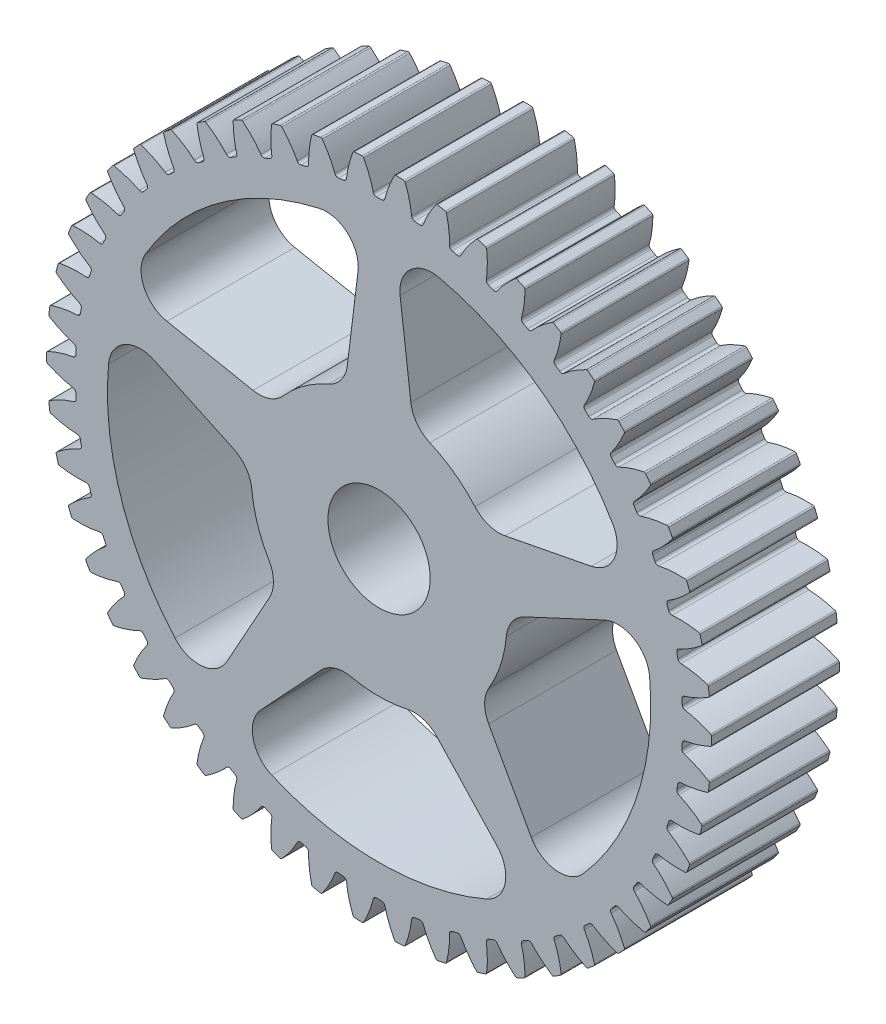
SolidWorks part; units mm, degrees
material "Alloy Steel"
ref_plane "Front" through (0, 0, 0) normal (0, 0, 1) x (1, 0, 0)
ref_plane "Top" through (0, 0, 0) normal (0, 1, 0) x (1, 0, 0)
ref_plane "Right" through (0, 0, 0) normal (1, 0, 0) x (0, 0, -1)
sketch "Sketch1" plane through (0, 0, 0) normal (0, 0, 1) x (1, 0, 0)
  circle A0 centre (0, 0) radius 33.02
  dimension "OutsideDiameter" = 66.04
extrude "Boss-Extrude1" add sketch "Sketch1" along normal blind 12.7
sketch "Sketch3" plane through (0, 0, 0) normal (0, 0, 1) x (1, 0, 0)
  line L0 (0, 0) -> (43.7181, 0) construction
  line L2 (0, 0) -> (-0.498, 30.1584) construction
  line L3 (0, 0) -> (0.498, 30.1584) construction
  line L4 (0.498, 30.1584) -> (0.4926, 29.8312) construction
  line L5 (0, 0) -> (0, 61.276) construction
  line L6 (-0.498, 30.1584) -> (-0.4926, 29.8312) construction
  circle A0 centre (0, 0) radius 33.02 construction
  circle A1 centre (0, 0) radius 31.75 construction
  circle A2 centre (0, 0) radius 29.8352 construction
  arc A3 (0.498, 30.1584) -> (-0.498, 30.1584) centre (0, 0) ccw construction
  arc A5 (1.5817, 32.9821) -> (-1.5817, 32.9821) centre (0, 0) ccw
  spline S0 degree 4 poles (-0.4926, 29.8312) (-0.4927, 29.8361) (-0.4933, 29.85) (-0.4949, 29.8763) (-0.4983, 29.9192) (-0.504, 29.9738) (-0.5128, 30.0443) (-0.5251, 30.1273) (-0.5406, 30.2184) (-0.5595, 30.3176) (-0.5803, 30.4164) (-0.6028, 30.5149) (-0.6268, 30.6129) (-0.6577, 30.7316) (-0.6973, 30.8738) (-0.7475, 31.0397) (-0.8089, 31.2277) (-0.8762, 31.4191) (-0.9464, 31.6071) (-1.0218, 31.7967) (-1.098, 31.98) (-1.1818, 32.1701) (-1.2615, 32.3454) (-1.3559, 32.5413) (-1.4337, 32.6994) (-1.5417, 32.9075) (-1.6071, 33.0302) (-1.6856, 33.1737) (-1.7214, 33.2374) (-1.7435, 33.2766) knots 0 0 0 0 0 0.005377 0.015084 0.028532 0.04661 0.064855 0.092111 0.119476 0.146842 0.174209 0.201575 0.228941 0.256307 0.307035 0.361767 0.4165 0.471232 0.525964 0.580697 0.635429 0.690161 0.744894 0.799626 0.854358 0.909091 0.954545 1 1 1 1 1 construction
  spline S1 degree 4 poles (-0.4926, 29.8312) (-0.4927, 29.8361) (-0.4933, 29.85) (-0.4949, 29.8763) (-0.4983, 29.9192) (-0.504, 29.9738) (-0.5128, 30.0443) (-0.5251, 30.1273) (-0.5406, 30.2184) (-0.5595, 30.3176) (-0.5803, 30.4164) (-0.6028, 30.5149) (-0.6268, 30.6129) (-0.6577, 30.7316) (-0.6973, 30.8738) (-0.7475, 31.0397) (-0.8089, 31.2277) (-0.8762, 31.4191) (-0.9464, 31.6071) (-1.0218, 31.7967) (-1.098, 31.98) (-1.1818, 32.1701) (-1.2615, 32.3454) (-1.3559, 32.5413) (-1.4337, 32.6994) (-1.5183, 32.8623) (-1.5601, 32.9416) (-1.5817, 32.9821) knots 0 0 0 0 0 0.005377 0.015084 0.028532 0.04661 0.064855 0.092111 0.119476 0.146842 0.174209 0.201575 0.228941 0.256307 0.307035 0.361767 0.4165 0.471232 0.525964 0.580697 0.635429 0.690161 0.744894 0.799626 0.854358 0.909091 0.909091 0.909091 0.909091 0.909091
  spline S2 degree 4 poles (0.4926, 29.8312) (0.4927, 29.8361) (0.4933, 29.85) (0.4949, 29.8763) (0.4983, 29.9192) (0.504, 29.9738) (0.5128, 30.0443) (0.5251, 30.1273) (0.5406, 30.2184) (0.5595, 30.3176) (0.5803, 30.4164) (0.6028, 30.5149) (0.6268, 30.6129) (0.6577, 30.7316) (0.6973, 30.8738) (0.7475, 31.0397) (0.8089, 31.2277) (0.8762, 31.4191) (0.9464, 31.6071) (1.0218, 31.7967) (1.098, 31.98) (1.1818, 32.1701) (1.2615, 32.3454) (1.3559, 32.5413) (1.4337, 32.6994) (1.5417, 32.9075) (1.6071, 33.0302) (1.6856, 33.1737) (1.7214, 33.2374) (1.7435, 33.2766) knots 0 0 0 0 0 0.005377 0.015084 0.028532 0.04661 0.064855 0.092111 0.119476 0.146842 0.174209 0.201575 0.228941 0.256307 0.307035 0.361767 0.4165 0.471232 0.525964 0.580697 0.635429 0.690161 0.744894 0.799626 0.854358 0.909091 0.954545 1 1 1 1 1 construction
  spline S3 degree 4 poles (0.4926, 29.8312) (0.4927, 29.8361) (0.4933, 29.85) (0.4949, 29.8763) (0.4983, 29.9192) (0.504, 29.9738) (0.5128, 30.0443) (0.5251, 30.1273) (0.5406, 30.2184) (0.5595, 30.3176) (0.5803, 30.4164) (0.6028, 30.5149) (0.6268, 30.6129) (0.6577, 30.7316) (0.6973, 30.8738) (0.7475, 31.0397) (0.8089, 31.2277) (0.8762, 31.4191) (0.9464, 31.6071) (1.0218, 31.7967) (1.098, 31.98) (1.1818, 32.1701) (1.2615, 32.3454) (1.3559, 32.5413) (1.4337, 32.6994) (1.5183, 32.8623) (1.5601, 32.9416) (1.5817, 32.9821) knots 0 0 0 0 0 0.005377 0.015084 0.028532 0.04661 0.064855 0.092111 0.119476 0.146842 0.174209 0.201575 0.228941 0.256307 0.307035 0.361767 0.4165 0.471232 0.525964 0.580697 0.635429 0.690161 0.744894 0.799626 0.854358 0.909091 0.909091 0.909091 0.909091 0.909091
  dimension "OutsideDiameter" = 66.04
  dimension "PitchCircle" = 63.5
  dimension "BaseCircle" = 59.6705
  dimension "DedendumCircle" = 60.325
sketch "DCLTBC" [suppressed] plane through (0, 0, 0) normal (0, 0, 1) x (1, 0, 0)
  line L0 (0, 0) -> (41.04, 0) construction
  line L1 (-0.5882, 26.2434) -> (-0.5952, 26.5563) construction
  line L2 (0.5882, 26.2434) -> (0.5952, 26.5563) construction
  line L3 (-0.5936, 26.4814) -> (-0.5952, 26.5563)
  line L4 (0.5936, 26.4814) -> (0.5952, 26.5563)
  line L5 (0, 0) -> (0, 104.9356) construction
  circle A0 centre (0, 0) radius 28.5
  circle A1 centre (0, 0) radius 27.5 construction
  circle A2 centre (0, 0) radius 26.563 construction
  arc A3 (0.5882, 26.2434) -> (-0.5882, 26.2434) centre (0, 0) ccw construction
  arc A4 (0.3512, 26.2477) -> (-0.3512, 26.2477) centre (0, 0) ccw
  arc A5 (-0.5936, 26.4814) -> (-0.3512, 26.2477) centre (-0.3544, 26.4868) ccw
  arc A7 (0.5936, 26.4814) -> (0.3512, 26.2477) centre (0.3544, 26.4868) cw
  spline S0 degree 4 poles (-999.0854, -27.9057) (-10.5882, 25.1883) (-0.7108, 25.7707) (-0.5671, 26.1913) (-0.5985, 26.609) (-0.6016, 26.6417) (-0.6063, 26.6839) (-0.6128, 26.7337) (-0.6209, 26.7885) (-0.6307, 26.8481) (-0.6414, 26.9075) (-0.653, 26.9669) (-0.6654, 27.026) (-0.6812, 27.0976) (-0.7015, 27.1836) (-0.7271, 27.2842) (-0.7584, 27.3983) (-0.7927, 27.5147) (-0.8284, 27.6294) (-0.8667, 27.7454) (-0.9054, 27.8577) (-0.948, 27.9745) (-0.9884, 28.0824) (-1.0364, 28.2034) (-1.2469, 28.7251) (-2.0615, 30.5023) (8.679, 5.7048) (-401.0337, 945.0216) knots -0.712101 -0.712101 -0.712101 -0.712101 -0.712101 0.005377 0.015084 0.028532 0.04661 0.064855 0.092111 0.119476 0.146842 0.174209 0.201575 0.228941 0.256307 0.307035 0.361767 0.4165 0.471232 0.525964 0.580697 0.635429 0.690161 0.744894 0.799626 0.854358 1.858481 1.858481 1.858481 1.858481 1.858481 only from (-0.5952, 26.5563) to (-1.151, 28.4767) construction
  spline S1 degree 4 poles (999.0854, -27.9056) (10.5882, 25.1883) (0.7108, 25.7707) (0.5671, 26.1913) (0.5985, 26.609) (0.6016, 26.6417) (0.6063, 26.6839) (0.6128, 26.7337) (0.6209, 26.7885) (0.6307, 26.8481) (0.6414, 26.9075) (0.653, 26.9669) (0.6654, 27.026) (0.6812, 27.0976) (0.7015, 27.1836) (0.7271, 27.2842) (0.7584, 27.3983) (0.7927, 27.5147) (0.8284, 27.6294) (0.8667, 27.7454) (0.9054, 27.8577) (0.948, 27.9745) (0.9884, 28.0824) (1.0364, 28.2034) (1.2469, 28.7251) (2.0615, 30.5023) (-8.679, 5.7048) (401.0337, 945.0216) knots -0.712101 -0.712101 -0.712101 -0.712101 -0.712101 0.005377 0.015084 0.028532 0.04661 0.064855 0.092111 0.119476 0.146842 0.174209 0.201575 0.228941 0.256307 0.307035 0.361767 0.4165 0.471232 0.525964 0.580697 0.635429 0.690161 0.744894 0.799626 0.854358 1.858481 1.858481 1.858481 1.858481 1.858481 only from (0.5952, 26.5563) to (1.151, 28.4767) construction
  spline S2 degree 4 poles (-0.5952, 26.5563) (-0.5953, 26.5593) (-0.5957, 26.5676) (-0.5966, 26.5833) (-0.5985, 26.609) (-0.6016, 26.6417) (-0.6063, 26.6839) (-0.6128, 26.7337) (-0.6209, 26.7885) (-0.6307, 26.8481) (-0.6414, 26.9075) (-0.653, 26.9669) (-0.6654, 27.026) (-0.6812, 27.0976) (-0.7015, 27.1836) (-0.7271, 27.2842) (-0.7584, 27.3983) (-0.7927, 27.5147) (-0.8284, 27.6294) (-0.8667, 27.7454) (-0.9054, 27.8577) (-0.948, 27.9745) (-0.9884, 28.0824) (-1.0364, 28.2034) (-1.0758, 28.3012) (-1.1188, 28.4023) (-1.14, 28.4516) (-1.151, 28.4767) knots 0 0 0 0 0 0.005377 0.015084 0.028532 0.04661 0.064855 0.092111 0.119476 0.146842 0.174209 0.201575 0.228941 0.256307 0.307035 0.361767 0.4165 0.471232 0.525964 0.580697 0.635429 0.690161 0.744894 0.799626 0.854358 0.909091 0.909091 0.909091 0.909091 0.909091
  spline S3 degree 4 poles (0.5952, 26.5563) (0.5953, 26.5593) (0.5957, 26.5676) (0.5966, 26.5833) (0.5985, 26.609) (0.6016, 26.6417) (0.6063, 26.6839) (0.6128, 26.7337) (0.6209, 26.7885) (0.6307, 26.8481) (0.6414, 26.9075) (0.653, 26.9669) (0.6654, 27.026) (0.6812, 27.0976) (0.7015, 27.1836) (0.7271, 27.2842) (0.7584, 27.3983) (0.7927, 27.5147) (0.8284, 27.6294) (0.8667, 27.7454) (0.9054, 27.8577) (0.948, 27.9745) (0.9884, 28.0824) (1.0364, 28.2034) (1.0758, 28.3012) (1.1188, 28.4023) (1.14, 28.4516) (1.151, 28.4767) knots 0 0 0 0 0 0.005377 0.015084 0.028532 0.04661 0.064855 0.092111 0.119476 0.146842 0.174209 0.201575 0.228941 0.256307 0.307035 0.361767 0.4165 0.471232 0.525964 0.580697 0.635429 0.690161 0.744894 0.799626 0.854358 0.909091 0.909091 0.909091 0.909091 0.909091
  dimension "OutsideDiameter" = 66.04
  dimension "PitchCircle" = 63.5
  dimension "BaseCircle" = 59.6705
  dimension "D1" = 0.3238
extrude "Cut-Extrude-DCLTBC" [suppressed] cut sketch "DCLTBC" along normal through all contours L4 S3 A0 S2 L3 A5 A4 A7
fillet "Fillet-DCLTBC" [suppressed] radius 0.1619
pattern_circular "CirPattern-DCLTBC" [suppressed] count 50 over 360 of bodies 111
sketch "DCGTBC" plane through (0, 0, 0) normal (0, 0, 1) x (1, 0, 0)
  line L0 (0, 0) -> (41.04, 0) construction
  line L5 (0, 0) -> (0, 104.9356) construction
  circle A0 centre (0, 0) radius 33.02
  circle A1 centre (0, 0) radius 31.75 construction
  circle A2 centre (0, 0) radius 29.8352 construction
  arc A3 (0.498, 30.1584) -> (-0.498, 30.1584) centre (0, 0) ccw construction
  arc A5 (0.2614, 30.1614) -> (0.5806, 30.4159) centre (0.2642, 30.4852) ccw
  arc A7 (-0.5806, 30.4159) -> (-0.2614, 30.1614) centre (-0.2642, 30.4852) ccw
  arc A11 (0.2614, 30.1614) -> (-0.2614, 30.1614) centre (0, 0) ccw
  spline S2 degree 4 poles (-999.5536, -12.7278) (-12.5544, 28.0053) (-0.6553, 28.7383) (-0.4506, 29.3302) (-0.4983, 29.9192) (-0.504, 29.9738) (-0.5128, 30.0443) (-0.5251, 30.1273) (-0.5406, 30.2184) (-0.5595, 30.3176) (-0.5803, 30.4164) (-0.6028, 30.5149) (-0.6268, 30.6129) (-0.6577, 30.7316) (-0.6973, 30.8738) (-0.7475, 31.0397) (-0.8089, 31.2277) (-0.8762, 31.4191) (-0.9464, 31.6071) (-1.0218, 31.7967) (-1.098, 31.98) (-1.1818, 32.1701) (-1.2615, 32.3454) (-1.3559, 32.5413) (-1.7288, 33.2996) (-3.049, 35.6508) (11.5222, 8.1522) (-473.0995, 914.7978) knots -0.593942 -0.593942 -0.593942 -0.593942 -0.593942 0.005377 0.015084 0.028532 0.04661 0.064855 0.092111 0.119476 0.146842 0.174209 0.201575 0.228941 0.256307 0.307035 0.361767 0.4165 0.471232 0.525964 0.580697 0.635429 0.690161 0.744894 0.799626 0.854358 1.740449 1.740449 1.740449 1.740449 1.740449 only from (-0.4926, 29.8312) to (-1.5817, 32.9821) construction
  spline S3 degree 4 poles (999.5536, -12.7278) (12.5544, 28.0053) (0.6553, 28.7383) (0.4506, 29.3302) (0.4983, 29.9192) (0.504, 29.9738) (0.5128, 30.0443) (0.5251, 30.1273) (0.5406, 30.2184) (0.5595, 30.3176) (0.5803, 30.4164) (0.6028, 30.5149) (0.6268, 30.6129) (0.6577, 30.7316) (0.6973, 30.8738) (0.7475, 31.0397) (0.8089, 31.2277) (0.8762, 31.4191) (0.9464, 31.6071) (1.0218, 31.7967) (1.098, 31.98) (1.1818, 32.1701) (1.2615, 32.3454) (1.3559, 32.5413) (1.7288, 33.2996) (3.049, 35.6508) (-11.5222, 8.1522) (473.0995, 914.7978) knots -0.593942 -0.593942 -0.593942 -0.593942 -0.593942 0.005377 0.015084 0.028532 0.04661 0.064855 0.092111 0.119476 0.146842 0.174209 0.201575 0.228941 0.256307 0.307035 0.361767 0.4165 0.471232 0.525964 0.580697 0.635429 0.690161 0.744894 0.799626 0.854358 1.740449 1.740449 1.740449 1.740449 1.740449 only from (0.4926, 29.8312) to (1.5817, 32.9821) construction
  spline S4 degree 4 poles (-0.5806, 30.4159) (-0.5833, 30.4283) (-0.5915, 30.4654) (-0.6058, 30.527) (-0.6268, 30.6129) (-0.6577, 30.7316) (-0.6973, 30.8738) (-0.7475, 31.0397) (-0.8089, 31.2277) (-0.8762, 31.4191) (-0.9464, 31.6071) (-1.0218, 31.7967) (-1.098, 31.98) (-1.1818, 32.1701) (-1.2615, 32.3454) (-1.3559, 32.5413) (-1.4337, 32.6994) (-1.5183, 32.8623) (-1.5601, 32.9416) (-1.5817, 32.9821) knots 0.160405 0.160405 0.160405 0.160405 0.160405 0.174209 0.201575 0.228941 0.256307 0.307035 0.361767 0.4165 0.471232 0.525964 0.580697 0.635429 0.690161 0.744894 0.799626 0.854358 0.909091 0.909091 0.909091 0.909091 0.909091
  spline S5 degree 4 poles (0.5806, 30.4159) (0.5833, 30.4283) (0.5915, 30.4654) (0.6058, 30.527) (0.6268, 30.6129) (0.6577, 30.7316) (0.6973, 30.8738) (0.7475, 31.0397) (0.8089, 31.2277) (0.8762, 31.4191) (0.9464, 31.6071) (1.0218, 31.7967) (1.098, 31.98) (1.1818, 32.1701) (1.2615, 32.3454) (1.3559, 32.5413) (1.4337, 32.6994) (1.5183, 32.8623) (1.5601, 32.9416) (1.5817, 32.9821) knots 0.160405 0.160405 0.160405 0.160405 0.160405 0.174209 0.201575 0.228941 0.256307 0.307035 0.361767 0.4165 0.471232 0.525964 0.580697 0.635429 0.690161 0.744894 0.799626 0.854358 0.909091 0.909091 0.909091 0.909091 0.909091
  dimension "OutsideDiameter" = 66.04
  dimension "PitchCircle" = 63.5
  dimension "BaseCircle" = 59.6705
  dimension "D1" = 0.3238
extrude "Cut-Extrude-DCGTBC" cut sketch "DCGTBC" along normal through all contours A5 S5 A0 S4 A7 A11 region at (0, 31.8529, 0)
fillet "Fillet-DCGTBC" radius 0.1619 2 edges at (1.5817, 32.9821, 6.35) (-1.5817, 32.9821, 6.35)
pattern_circular "CirPattern-DCGTBC" count 50 over 360 about axis through (0, 0, 12.7) along (0, 0, 1) of "Cut-Extrude-DCGTBC", "Fillet-DCGTBC"
sketch "Sketch4" plane through (0, 0, 12.7) normal (0, 0, 1) x (1, 0, 0)
  circle A0 centre (0, 0) radius 4.7625
  dimension "D1" = 9.525
extrude "Cut-Extrude2" cut sketch "Sketch4" against normal through all
sketch "Sketch5" plane through (0, 0, 0) normal (0, 0, -1) x (-1, 0, 0)
  circle A0 centre (0, 0) radius 5.08
  dimension "D1" = 10.16
extrude "Cut-Extrude3" cut sketch "Sketch5" against normal through all
sketch "Sketch6" plane through (0, 0, 0) normal (0, 0, -1) x (-1, 0, 0)
  circle A0 centre (0, 0) radius 5.08 construction
  circle A1 centre (0, 0) radius 5.08
  circle A2 centre (0, 0) radius 6.35
  dimension "D1" = 12.7
extrude "Cut-Extrude4" cut sketch "Sketch6" against normal blind 3.9688
sketch "Sketch7" plane through (0, 0, 12.7) normal (0, 0, 1) x (1, 0, 0)
  line L0 (0, 0) -> (0, 26.9875) construction
  line L1 (-3.3927, 12.2384) -> (-1.5875, 26.9408)
  line L2 (3.3927, 12.2384) -> (1.5875, 26.9408)
  line L3 (10.591, 7.0086) -> (25.1316, 9.835)
  line L4 (12.6879, 0.5552) -> (26.1128, 6.8154)
  line L5 (9.9383, -7.9069) -> (17.1197, -20.8624)
  line L6 (4.4488, -11.8953) -> (14.5511, -22.7286)
  line L7 (-4.4488, -11.8953) -> (-14.5511, -22.7286)
  line L8 (-9.9383, -7.9069) -> (-17.1197, -20.8624)
  line L9 (-12.6879, 0.5552) -> (-26.1128, 6.8154)
  line L10 (-10.591, 7.0086) -> (-25.1316, 9.835)
  circle A0 centre (0, 0) radius 26.9875
  circle A1 centre (0, 0) radius 12.7
  point P28 (0, 0)
  dimension "D1" = 53.975
  dimension "D2" = 25.4
  dimension "D3" = 7
  dimension "D4" = 3.175
  dimension "D5" = 5
extrude "Cut-Extrude5" cut sketch "Sketch7" against normal through all contours A1 L1 A0 L10 | A1 L9 A0 L8 | A1 L3 A0 L2 | A1 L5 A0 L4 | A1 L7 A0 L6 region at (-11.8694, 16.3368, 12.7) region at (11.8694, 16.3368, 12.7) region at (-19.2051, -6.2401, 12.7) region at (19.2051, -6.2401, 12.7) region at (0, -20.1934, 12.7)
fillet "Fillet1" radius 3.175 20 edges at (-3.3927, 12.2384, 6.35) (-10.591, 7.0086, 6.35) (-1.5875, 26.9408, 6.35) (-25.1316, 9.835, 6.35) (-9.9383, -7.9069, 6.35) (-12.6879, 0.5552, 6.35) (-26.1128, 6.8154, 6.35) (-17.1197, -20.8624, 6.35) (14.5511, -22.7286, 6.35) (-4.4488, -11.8953, 6.35) (4.4488, -11.8953, 6.35) (1.5875, 26.9408, 6.35) (25.1316, 9.835, 6.35) (26.1128, 6.8154, 6.35) (17.1197, -20.8624, 6.35) (-14.5511, -22.7286, 6.35) (12.6879, 0.5552, 6.35) (9.9383, -7.9069, 6.35) (10.591, 7.0086, 6.35) (3.3927, 12.2384, 6.35)
equation "\"DiametralPitch\"= 20'Diametral Pitch"
equation "\"NumTeeth\"= 50'Number of Teeth"
equation "\"PressureAngle\"= 20deg'Pressure Angle"
equation "\"Addendum\"= 1 / \"DiametralPitch\"'Addendum"
equation "\"Dedendum\"= 1.25 / \"DiametralPitch\"'Dedendum"
equation "\"WorkingDepth\"= 2 / \"DiametralPitch\"'Working Depth - here for REF (Not used in building model)"
equation "\"WholeDepth\"= 2.25 / \"DiametralPitch\"'Whole Depth - here for REF (Not used in building model)"
equation "\"Clearance\"= .19 / \"DiametralPitch\"'Clearance"
equation "\"CircularPitch\"= pi / \"DiametralPitch\"'Circular Pitch - here for REF (Not used in building model)"
equation "\"PitchCircle\"= \"NumTeeth\" / \"DiametralPitch\"'Pitch Circle - or - Pitch Diameter"
equation "\"OutsideDiameter\"= ( \"NumTeeth\" + 2 ) / \"DiametralPitch\"'Outside Diameter"
equation "\"Fillet\"= \"Clearance\" * cos ( \"PressureAngle\" ) * tan ( ( 90 + \"PressureAngle\" ) / 2 )'Fillet"
equation "\"AddendumCircle\"= \"PitchCircle\" + ( 2 * \"Addendum\" )'Addendum Circle - or - Addendum Diameter"
equation "\"DedendumCircle\"= \"PitchCircle\" - ( 2 * \"Dedendum\" )'Dedendum Circle - or - Dedendum Diameter"
equation "\"BaseCircle\"= \"PitchCircle\" * cos ( \"PressureAngle\" )'Base Circle - Base Diameter"
equation "\"PitchAngle\"= 360deg / \"NumTeeth\"'Pitch Angle"
equation "\"Alpha\"= sqr ( \"PitchCircle\" ^ 2 - \"BaseCircle\" ^ 2 ) / \"BaseCircle\" * 180 / PI - \"PressureAngle\"'Alpha - Used for Calculating Beta"
equation "\"Beta\"= ( \"PitchAngle\" / 4 - ( \"Alpha\" - 90 ) )'Beta - Used in definition of the parameters for the parametric equation driven curve"
equation "\"Gamma\"= ( \"PitchAngle\" / 4 - ( \"Alpha\" + 90 ) )'Gamma - Used in definition of the parameters for the parametric equation driven curve"
equation "\"Phi\"= sqr ( ( \"AddendumCircle\" / 2 ) ^ 2 - ( \"BaseCircle\" / 2 ) ^ 2 ) / ( \"BaseCircle\" / 2 )'Phi - Used in definition of the parameters for the parametric equation driven curve"
equation "\"DCGTBC\"= iif ( ( \"DedendumCircle\" + ( \"Fillet\" * 2 ) ) > \"BaseCircle\" , \"unsuppressed\" , \"suppressed\" )'if Dedendum Circle +2X Fillet IS GREATER THAN BaseCircle THEN Unsuppress OR Suppress FEATURE"
equation "\"DCLTBC\"= iif ( ( \"DedendumCircle\" + ( \"Fillet\" * 2 ) ) > \"BaseCircle\" , \"suppressed\" , \"unsuppressed\" )'if Dedendum Circle +2X Fillet IS GREATER THAN BaseCircle THEN Suppress OR Unsuppress FEATURE"
equation "\"Cut-Extrude-DCGTBC\"= iif ( ( \"DedendumCircle\" + ( \"Fillet\" * 2 ) ) > \"BaseCircle\" , \"unsuppressed\" , \"suppressed\" )'if Dedendum Circle +2X Fillet IS GREATER THAN BaseCircle THEN UnsuppressORSuppress FEATURE"
equation "\"Cut-Extrude-DCLTBC\"= iif ( ( \"DedendumCircle\" + ( \"Fillet\" * 2 ) ) > \"BaseCircle\" , \"suppressed\" , \"unsuppressed\" )'if Dedendum Circle +2X Fillet IS GREATER THAN BaseCircle THEN SuppressORUnsuppress FEATURE"
equation "\"CirPattern-DCGTBC\"= iif ( ( \"DedendumCircle\" + ( \"Fillet\" * 2 ) ) > \"BaseCircle\" , \"unsuppressed\" , \"suppressed\" )'if Dedendum Circle +2X Fillet IS GREATER THAN \"BaseCircle\" THEN UnsuppressORSuppress FEATURE"
equation "\"CirPattern-DCLTBC\"= iif ( ( \"DedendumCircle\" + ( \"Fillet\" * 2 ) ) > \"BaseCircle\" , \"suppressed\" , \"unsuppressed\" )'if Dedendum Circle +2X Fillet IS GREATER THAN \"BaseCircle\" THEN SuppressORUnsuppress FEATURE"
equation "\"Fillet-DCGTBC\"= iif ( ( \"DedendumCircle\" + ( \"Fillet\" * 2 ) ) > \"BaseCircle\" , \"unsuppressed\" , \"suppressed\" )'if Dedendum Circle +2X Fillet IS GREATER THAN \"BaseCircle\" THEN UnsuppressORSuppress FEATURE"
equation "\"Fillet-DCLTBC\"= iif ( ( \"DedendumCircle\" + ( \"Fillet\" * 2 ) ) > \"BaseCircle\" , \"suppressed\" , \"unsuppressed\" )'if Dedendum Circle +2X Fillet IS GREATER THAN \"BaseCircle\" THEN SuppressORUnsuppress FEATURE"
equation "\"D1@CirPattern-DCGTBC\"=\"NumTeeth\""
equation "\"D1@CirPattern-DCLTBC\"=\"NumTeeth\""
equation "\"D1@DCGTBC\"=\"Fillet\""
equation "\"D1@DCLTBC\"=\"Fillet\""
equation "\"D1@Fillet-DCLTBC\"=\"Fillet\"/2"
equation "\"D1@Fillet-DCGTBC\"=\"Fillet\"/2"
